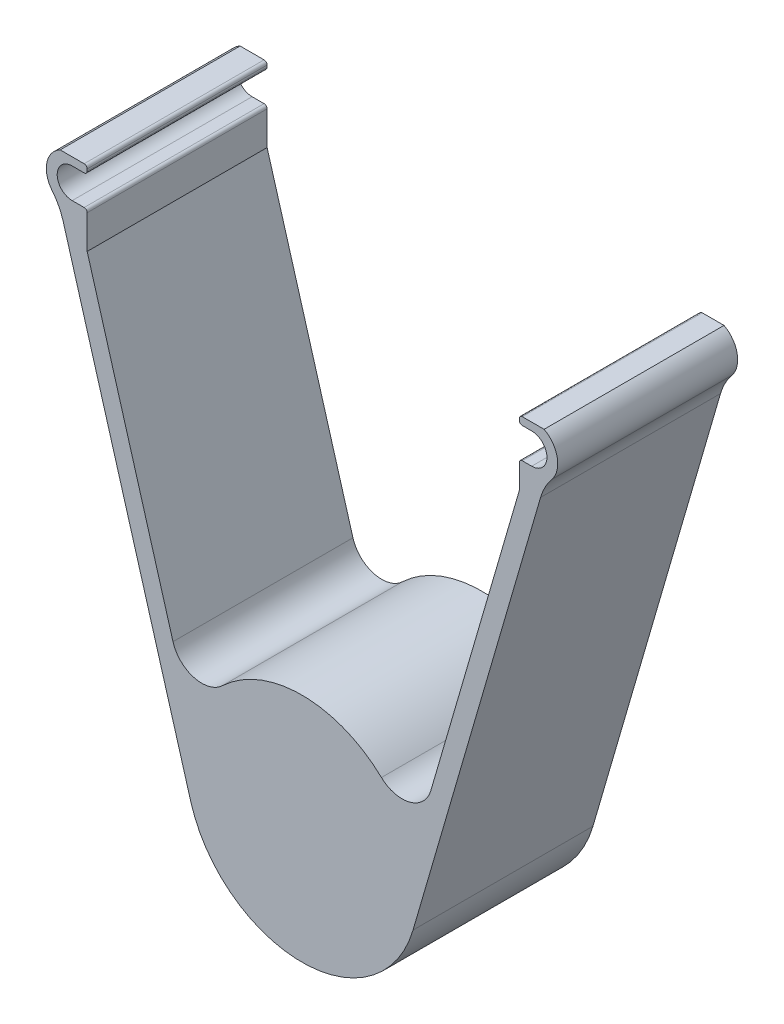
SolidWorks part; units mm, degrees
ref_plane "Front Plane" through (0, 0, 0) normal (0, 0, 1) x (1, 0, 0)
ref_plane "Top Plane" through (0, 0, 0) normal (0, 1, 0) x (1, 0, 0)
ref_plane "Right Plane" through (0, 0, 0) normal (1, 0, 0) x (0, 0, -1)
sketch "Sketch1" plane through (0, 0, 0) normal (0, 0, 1) x (1, 0, 0)
  line L6 (-35.807, 65.4375) -> (-21.497, 16.2472)
  line L8 (36.2341, 66.9059) -> (21.497, 16.2472)
  line L17 (39.7899, 67.7154) -> (18.5233, -5.3886)
  line L18 (-39.8147, 67.8005) -> (-18.5233, -5.3886)
  line L34 (-39.8353, 77.8524) -> (-36.807, 77.8524)
  line L35 (39.8353, 77.8524) -> (40.3798, 77.8524)
  line L36 (-39.8353, 77.8524) -> (-40.307, 77.8524)
  line L40 (36.2341, 77.0752) -> (36.2341, 77.3524)
  line L42 (36.2341, 70.9868) -> (36.2341, 66.9059)
  line L43 (36.7341, 77.8524) -> (39.8353, 77.8524)
  line L45 (-38.307, 71.5312) -> (-36.307, 71.5312)
  line L46 (-35.807, 71.0312) -> (-35.807, 65.4375)
  line L47 (-36.807, 77.8524) -> (-36.307, 77.8524)
  line L48 (-35.807, 77.3524) -> (-35.807, 77.0313)
  line L49 (38.307, 71.4868) -> (36.7341, 71.4868)
  line L50 (-38.307, 76.5313) -> (-36.307, 76.5313)
  line L51 (38.307, 76.5752) -> (36.7341, 76.5752)
  arc A10 (-40.307, 77.8524) -> (-41.6546, 71.312) centre (-38.307, 74.0312) ccw
  arc A11 (41.6658, 71.2709) -> (40.3798, 77.8524) centre (38.307, 74.031) ccw
  arc A16 (41.6658, 71.2709) -> (39.7899, 67.7154) centre (49.3919, 64.9221) ccw
  arc A17 (-39.8147, 67.8005) -> (-41.6546, 71.312) centre (-49.4166, 65.0072) ccw
  arc A23 (36.2341, 77.3524) -> (36.7341, 77.8524) centre (36.7341, 77.3524) cw
  arc A24 (-38.307, 76.5313) -> (-38.307, 71.5312) centre (-38.307, 74.0312) ccw
  arc A25 (38.307, 71.4868) -> (38.307, 76.5752) centre (38.307, 74.031) ccw
  arc A26 (-36.307, 71.5312) -> (-35.807, 71.0312) centre (-36.307, 71.0312) cw
  arc A27 (36.7341, 71.4868) -> (36.2341, 70.9868) centre (36.7341, 70.9868) ccw
  arc A28 (36.7341, 76.5752) -> (36.2341, 77.0752) centre (36.7341, 77.0752) cw
  arc A29 (-36.307, 76.5313) -> (-35.807, 77.0313) centre (-36.307, 77.0313) ccw
  arc A30 (-36.307, 77.8524) -> (-35.807, 77.3524) centre (-36.307, 77.3524) cw
  arc A31 (13.2594, 14.0121) -> (-13.2594, 14.0121) centre (0, 0) ccw
  arc A32 (-18.5233, -5.3886) -> (18.5233, -5.3886) centre (0, 0) ccw
  arc A33 (21.497, 16.2472) -> (13.2594, 14.0121) centre (16.6961, 17.6438) cw
  arc A34 (-21.497, 16.2472) -> (-13.2594, 14.0121) centre (-16.6961, 17.6438) ccw
  point P0 (0, 0)
  point P2 (0, 77.0313)
  point P10 (42.5, 77.0313)
  point P16 (0, 77.0313)
  point P17 (-42.5, 77.0313)
  point P24 (0, 74.0312)
  point P32 (3.1881, -46.6897)
  point P57 (36.2341, 77.8524)
  dimension "D2" = 5
  dimension "D3" = 10
  dimension "D4" = 0.5
  dimension "D1" = 85
extrude "Boss-Extrude1" add sketch "Sketch1" along normal blind 30 contours L43 L35 A11 A16 L17 A32 L18 A17 A10 L36 L34 L47 A30 L48 A29 L50 A24 L45 A26 L46 L6 A34 A31 A33 L8 L42 A27 L49 A25 L51 A28 L40 A23
